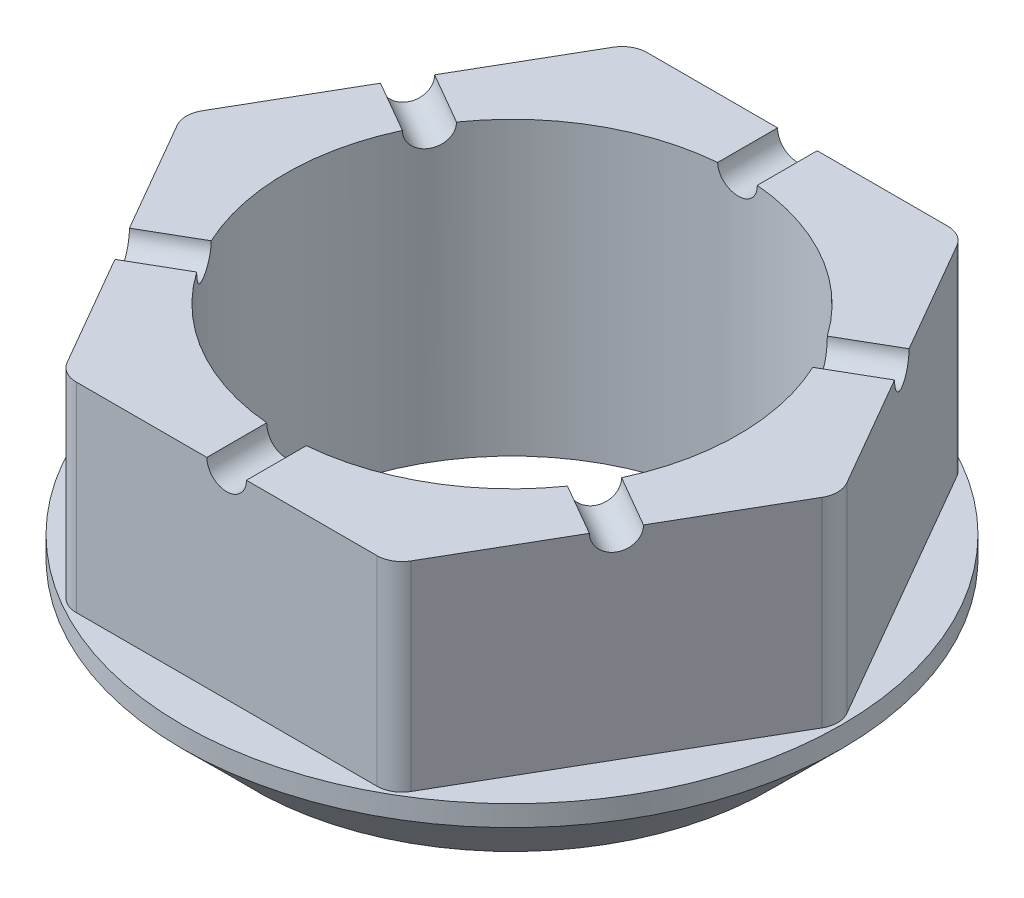
SolidWorks part; units mm, degrees
note: '?' marks a value the reader was unsure of.
material "6061-T6 (SS)"
ref_plane "X-Y Datum" through (0, 0, 0) normal (0, 0, 1) x (1, 0, 0)
ref_plane "X-Z Datum" through (0, 0, 0) normal (0, 1, 0) x (1, 0, 0)
ref_plane "Y-Z Datum" through (0, 0, 0) normal (1, 0, 0) x (0, 0, -1)
sketch "Sketch1" plane through (0, 0, 0) normal (1, 0, 0) x (0, 0, -1)
  line L0 (0, 0) -> (0, 50000) construction
  line L1 (0, 0) -> (-50000, 0) construction
  line L2 (-22.6695, -29.21) -> (-22.6695, 0)
  line L3 (-22.6695, 0) -> (-33, 0)
  line L4 (-33, 0) -> (-33, -22.0794)
  line L6 (-33, -22.0794) -> (-25.8445, -29.21)
  line L7 (-25.8445, -29.21) -> (-22.6695, -29.21)
  dimension "D1" = 66
  dimension "D2" = 3.175
  dimension "D3" = 29.21
  dimension "D4" = 45.339
  dimension "D5" = 45.1
  dimension "D6" = 22.0794
revolve "Revolve1" add sketch "Sketch1" angle 360 about L0
ref_axis "Axis1" through (0, 2.4756, 0) along (0, -1, 0)?
thread "Thread1" [suppressed] pitch 2.1167 start angle 0, offset 0, length 0, pitch 2.1167, diameter 45.339
ref_plane "Plane1" through (22.6695, -31.75, 0) normal (0, 0, 1) x (1, 0, 0)
sketch "Thread Profile1" plane through (22.6695, -31.75, 0) normal (0, 0, 1) x (1, 0, 0)
  line L0 (0, 0) -> (0, 2.1167) construction
  line L1 (0, 0) -> (1.1457, 0.6615)
  line L2 (1.1457, 0.6615) -> (1.1457, 0.926)
  line L3 (1.1457, 0.926) -> (0, 1.5875)
  line L4 (1.1457, 0.7937) -> (0, 0.7937) construction
  line L11 (0, 0) -> (0, 1.5875)
  point P2 (0, 0)
  dimension "Pitch" = 2.1167
  dimension "Profile_Angle" = 60
  dimension "Profile_Land" = 0.2646
  dimension "Profile_Height" = 1.1457
sketch "Sketch4" plane through (0, 0, 0) normal (0, 1, 0) x (1, 0, 0)
  line L1 (16.5, 28.5788) -> (-16.5, 28.5788)
  line L2 (-16.5, 28.5788) -> (-33, 0)
  line L3 (-33, 0) -> (-16.5, -28.5788)
  line L4 (-16.5, -28.5788) -> (16.5, -28.5788)
  line L5 (16.5, -28.5788) -> (33, 0)
  line L6 (33, 0) -> (16.5, 28.5788)
  circle A0 centre (0, 0) radius 28.5788 construction
  circle A1 centre (0, 0) radius 33 construction
  circle A2 centre (0, 0) radius 33 construction
  point P14 (0, 28.5788)
  circle M16 centre (0, 0) radius 33
extrude "Cut-Extrude5" cut sketch "Sketch4" against normal blind 20 contours L6 L5 L4 L3 L2 L1 M16 | L1 M16 | L2 M16 | L3 M16 | L4 M16 | L5 M16
fillet "Fillet4" radius 2.5 6 edges at (16.5, -10, 28.5788) (33, -10, 0) (16.5, -10, -28.5788) (-16.5, -10, -28.5788) (-33, -10, 0) (-16.5, -10, 28.5788)
sketch "Sketch7" plane through (0, 0, 0) normal (0, 0, 1) x (1, 0, 0)
  circle A1 centre (0, 0) radius 1.9844
  dimension "D2" = 3.9688
extrude "Cut-Extrude6" cut sketch "Sketch7" along normal through all both and the other way through all from surface at -28.5788 starting at face at (0, -10, -28.5788)
pattern_circular "CirPattern2" count 6 over 360 about axis through (0, 0, 0) along (0, -1, 0) of "Cut-Extrude6"
